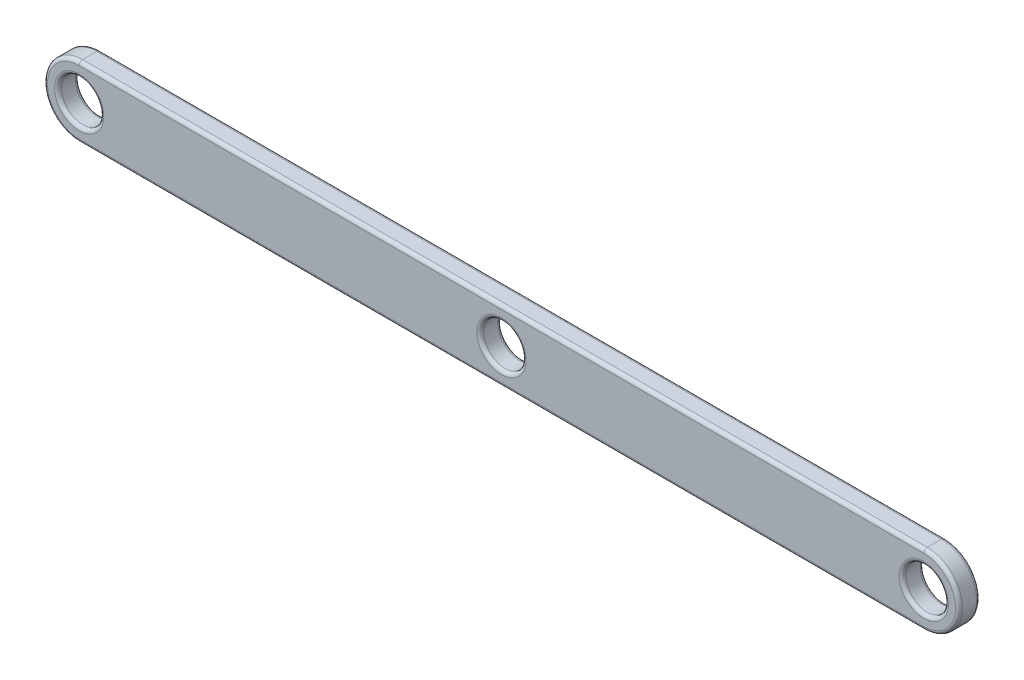
SolidWorks part; units mm, degrees
material "AR-M2"
ref_plane "正面" through (0, 0, 0) normal (0, 0, 1) x (1, 0, 0)
ref_plane "平面" through (0, 0, 0) normal (0, 1, 0) x (1, 0, 0)
ref_plane "右側面" through (0, 0, 0) normal (1, 0, 0) x (0, 0, -1)
sketch "ｽｹｯﾁ1" plane through (0, 0, 0) normal (0, 0, 1) x (1, 0, 0)
  line L0 (0, 0) -> (120, 0) construction
  line L1 (0, 5) -> (120, 5)
  line L2 (120, -5) -> (0, -5)
  circle A0 centre (60, 0) radius 3
  circle A1 centre (120, 0) radius 3
  circle A2 centre (0, 0) radius 3
  arc A3 (0, 5) -> (0, -5) centre (0, 0) ccw
  arc A4 (120, -5) -> (120, 5) centre (120, 0) ccw
  dimension "D3" = 6
  dimension "D4" = 6
  dimension "D5" = 6
  dimension "D6" = 10
  dimension "D7" = 10
  dimension "D1" = 120
extrude "ﾎﾞｽ - 押し出し1" add sketch "ｽｹｯﾁ1" along normal blind 3
fillet "ﾌｨﾚｯﾄ1" radius 0.5 14 edges at (3, 0, 0) (63, 0, 0) (60, -5, 0) (125, 0, 0) (60, 5, 0) (-5, 0, 0) (123, 0, 0) (3, 0, 3) (63, 0, 3) (60, 5, 3) (125, 0, 3) (60, -5, 3) (-5, 0, 3) (123, 0, 3)
